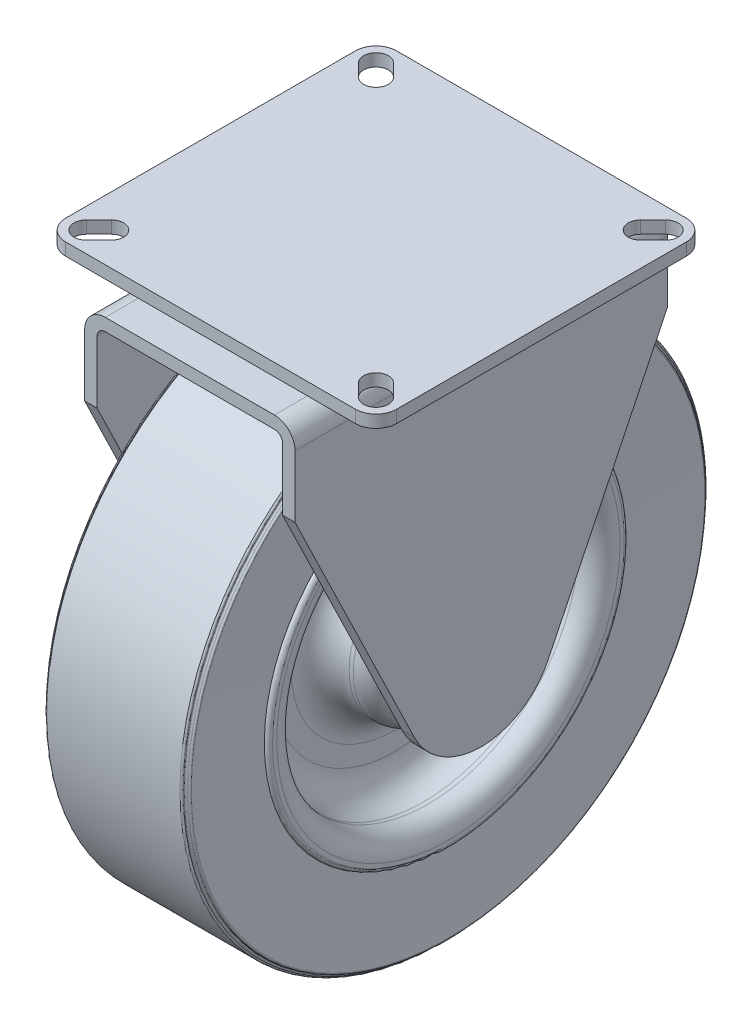
SolidWorks part; units mm, degrees
ref_plane "Front Plane" through (0, 0, 0) normal (0, 0, 1) x (1, 0, 0)
ref_plane "Top Plane" through (0, 0, 0) normal (0, 1, 0) x (1, 0, 0)
ref_plane "Right Plane" through (0, 0, 0) normal (1, 0, 0) x (0, 0, -1)
sketch "Sketch1" plane through (0, 0, 0) normal (0, 0, 1) x (1, 0, 0)
  line L0 (-16.5, 10) -> (16.5, 10)
  line L1 (-16.5, 43.5) -> (16.5, 43.5)
  line L2 (-17.5, 42.5) -> (-17.5, 11)
  line L3 (-25.7789, 0) -> (30.9257, 0) construction
  line L4 (17.5, 42.5) -> (17.5, 11)
  line L5 (11.5, 36.5) -> (12.5, 36.5)
  line L6 (-17.5, 10) -> (17.5, 10)
  line L7 (-17.5, 10) -> (-17.5, 13)
  line L8 (-12.5, 18) -> (-11.5, 18)
  line L9 (17.5, 10) -> (17.5, 13)
  line L10 (-17.5, 43.5) -> (17.5, 43.5)
  line L11 (-17.5, 43.5) -> (-17.5, 41.5)
  line L12 (-12.5, 36.5) -> (-11.5, 36.5)
  line L13 (17.5, 43.5) -> (17.5, 41.5)
  line L14 (11.5, 18) -> (12.5, 18)
  line L15 (-4.5, 29.5) -> (-4.5, 25)
  line L17 (4.5, 29.5) -> (4.5, 25)
  arc A0 (-17.5, 41.5) -> (-12.5, 36.5) centre (-12.5, 41.5) ccw
  arc A1 (17.5, 41.5) -> (12.5, 36.5) centre (12.5, 41.5) cw
  arc A2 (17.5, 13) -> (12.5, 18) centre (12.5, 13) ccw
  arc A3 (-17.5, 13) -> (-12.5, 18) centre (-12.5, 13) cw
  arc A4 (-16.5, 10) -> (-17.5, 11) centre (-16.5, 11) cw
  arc A5 (16.5, 10) -> (17.5, 11) centre (16.5, 11) ccw
  arc A6 (16.5, 43.5) -> (17.5, 42.5) centre (16.5, 42.5) cw
  arc A7 (-16.5, 43.5) -> (-17.5, 42.5) centre (-16.5, 42.5) ccw
  arc A8 (11.5, 18) -> (4.5, 25) centre (11.5, 25) cw
  arc A9 (-4.5, 25) -> (-11.5, 18) centre (-11.5, 25) cw
  arc A10 (-11.5, 36.5) -> (-4.5, 29.5) centre (-11.5, 29.5) cw
  arc A11 (11.5, 36.5) -> (4.5, 29.5) centre (11.5, 29.5) ccw
  point P0 (0, 0)
  point P21 (17.5, 36.5)
  point P24 (17.5, 18)
  point P41 (4.5, 18)
  dimension "D7" = 5
  dimension "D8" = 1
  dimension "D9" = 7
  dimension "D1" = 8
  dimension "D2" = 35
  dimension "D3" = 33.5
  dimension "D4" = 7
  dimension "D5" = 13
  dimension "D6" = 13
revolve "Revolve1" add sketch "Sketch1" angle 360 about L3 region at (0, 26.4263, 0)
sketch "Sketch2" plane through (0, 0, 0) normal (0, 0, 1) x (1, 0, 0)
  line L0 (-24.9917, 0) -> (28.5899, 0) construction
  line L2 (-16.5, 43.5) -> (16.5, 43.5)
  line L3 (-16.5, 62.9) -> (-16.5, 63.1)
  line L4 (-16.1, 63.5) -> (16.1, 63.5)
  line L5 (16.5, 62.9) -> (16.5, 63.1)
  line L7 (-16.5, 43.5) -> (-17.429, 62.08)
  line L10 (-16.5, 63.5) -> (-16.5, 62.5)
  line L11 (-16.9, 62.5) -> (-17.0295, 62.5)
  line L14 (16.9, 62.5) -> (17.0295, 62.5)
  line L15 (16.5, 43.5) -> (17.429, 62.08)
  arc A0 (-16.5, 63.1) -> (-16.1, 63.5) centre (-16.1, 63.1) cw
  arc A1 (-16.5, 62.9) -> (-16.9, 62.5) centre (-16.9, 62.9) cw
  arc A2 (-17.429, 62.08) -> (-17.0295, 62.5) centre (-17.0295, 62.1) cw
  arc A3 (17.429, 62.08) -> (17.0295, 62.5) centre (17.0295, 62.1) ccw
  arc A4 (16.9, 62.5) -> (16.5, 62.9) centre (16.9, 62.9) cw
  arc A5 (16.1, 63.5) -> (16.5, 63.1) centre (16.1, 63.1) cw
  point P23 (16.5, 62.5)
  point P30 (16.5, 63.5)
  dimension "D2" = 0.4
  dimension "D1" = 20
revolve "Revolve3" add sketch "Sketch2" angle 360 about L0 region at (0, 53.5699, 0)
sketch "Sketch5" plane through (0, 0, 0) normal (0, 0, 1) x (1, 0, 0)
  line L0 (-17.429, 62.08) -> (-17.429, -62.08) construction
  line L1 (22.429, -18) -> (25.429, -18)
  line L2 (-22.429, -15) -> (-22.429, 66.5)
  line L3 (-20.429, 68.5) -> (20.429, 68.5)
  line L4 (22.429, -15) -> (22.429, 66.5)
  line L5 (17.429, 62.08) -> (17.429, -62.08) construction
  line L6 (16.1, 63.5) -> (-16.1, 63.5) construction
  line L7 (-20.429, 71.5) -> (20.429, 71.5)
  line L8 (25.429, -18) -> (25.429, 66.5)
  line L9 (-25.429, -18) -> (-22.429, -18)
  line L10 (-25.429, -18) -> (-25.429, 66.5)
  line L11 (22.429, -15) -> (22.429, -18)
  line L12 (-22.429, -15) -> (-22.429, -18)
  line L13 (-22.429, -15) -> (22.429, -15) construction
  line L15 (-25.429, -18) -> (25.429, -18) construction
  arc A0 (-22.429, 66.5) -> (-20.429, 68.5) centre (-20.429, 66.5) cw
  arc A1 (20.429, 68.5) -> (22.429, 66.5) centre (20.429, 66.5) cw
  arc A2 (20.429, 71.5) -> (25.429, 66.5) centre (20.429, 66.5) cw
  arc A3 (-25.429, 66.5) -> (-20.429, 71.5) centre (-20.429, 66.5) cw
  dimension "D5" = 2
  dimension "D1" = 5
  dimension "D2" = 5
  dimension "D3" = 5
  dimension "D6" = 3
extrude "Boss-Extrude2" add sketch "Sketch5" along normal blind 90 from offset 45 separate body offset against normal yes
sketch "Sketch6" plane through (-25.429, 0, 0) normal (-1, 0, 0) x (0, 0, 1)
  line L0 (45, 66.5) -> (45, -18) construction
  line L5 (-45, 51.5) -> (-16.1938, -7.8587)
  line L6 (45, 51.5) -> (16.1938, -7.8587)
  line L7 (-45, 51.5) -> (-45, -18)
  line L8 (-45, -18) -> (45, -18)
  line L9 (45, -18) -> (45, 51.5)
  arc A0 (-16.1938, -7.8587) -> (16.1938, -7.8587) centre (0, 0) ccw
  line M1 (-45, 66.5) -> (-45, -18)
  line M2 (-45, -18) -> (45, -18)
  line M3 (45, -18) -> (45, 66.5)
extrude "Cut-Extrude1" cut sketch "Sketch6" against normal blind 3 contours A0 L8 L6 M3 | A0 L5 M1 M2 region at (-25.429, 4.7857, 33.3258) region at (-25.429, 4.7857, -33.3258)
extrude "Cut-Extrude2" cut sketch "Sketch6<3>" against normal through all from offset 47 contours A0 L8 L6 M3 | A0 L5 M1 M2 region at (-25.429, 4.7857, 33.3258) region at (-25.429, 4.7857, -33.3258) offset against normal yes
sketch "Sketch6<3>" plane through (-25.429, 0, 0) normal (-1, 0, 0) x (0, 0, 1) same geometry as "Sketch6"
sketch "Sketch7" plane through (-25.429, 0, 0) normal (-1, 0, 0) x (0, 0, 1)
  circle A0 centre (0, 0) radius 10
extrude "Boss-Extrude3" add sketch "Sketch7" against normal through all
sketch "Sketch8" plane through (0, 71.5, 0) normal (0, 1, 0) x (1, 0, 0)
  circle A0 centre (0, 0) radius 18
  circle A1 centre (0, 0) radius 20
extrude "Boss-Extrude4" add sketch "Sketch8" along normal blind 3
sketch "Sketch9" plane through (0, 74.5, 0) normal (0, 1, 0) x (1, 0, 0)
  line L1 (-35, 40) -> (35, 40)
  line L2 (-40, 35) -> (-40, -35)
  line L3 (-35, -40) -> (35, -40)
  line L4 (40, 35) -> (40, -35)
  line L5 (-40, 40) -> (40, -40) construction
  line L6 (-40, -40) -> (40, 40) construction
  arc A0 (35, -40) -> (40, -35) centre (35, -35) ccw
  arc A1 (-40, -35) -> (-35, -40) centre (-35, -35) ccw
  arc A2 (-35, 40) -> (-40, 35) centre (-35, 35) ccw
  arc A3 (35, 40) -> (40, 35) centre (35, 35) cw
  point P0 (0, 0)
  dimension "D3" = 5
  dimension "D1" = 80
  dimension "D2" = 80
extrude "Boss-Extrude5" add sketch "Sketch9" along normal blind 3
sketch "Sketch10" plane through (0, 77.5, 0) normal (0, 1, 0) x (1, 0, 0)
  line L0 (0, 45) -> (0, -45) construction
  line L1 (20.429, 45) -> (-20.429, 45) construction
  line L2 (20.429, -45) -> (-20.429, -45) construction
  line L3 (-40, 0) -> (40, 0) construction
  line L4 (-40, 35) -> (-40, -35) construction
  line L5 (40, -35) -> (40, 35) construction
  line L6 (35, 40) -> (-35, 40) construction
  line L7 (-37.1213, 32.8787) -> (-34.1213, 29.8787)
  line L8 (29.8787, 34.1213) -> (32.8787, 37.1213)
  line L9 (-29.8787, 34.1213) -> (-32.8787, 37.1213)
  line L10 (37.1213, 32.8787) -> (34.1213, 29.8787)
  line L11 (37.1213, -32.8787) -> (34.1213, -29.8787)
  line L12 (-29.8787, -34.1213) -> (-32.8787, -37.1213)
  line L13 (29.8787, -34.1213) -> (32.8787, -37.1213)
  line L14 (-37.1213, -32.8787) -> (-34.1213, -29.8787)
  arc A0 (-32.8787, 37.1213) -> (-37.1213, 32.8787) centre (-35, 35) ccw
  arc A1 (-34.1213, 29.8787) -> (-29.8787, 34.1213) centre (-32, 32) ccw
  arc A2 (34.1213, 29.8787) -> (29.8787, 34.1213) centre (32, 32) cw
  arc A3 (32.8787, 37.1213) -> (37.1213, 32.8787) centre (35, 35) cw
  arc A4 (32.8787, -37.1213) -> (37.1213, -32.8787) centre (35, -35) ccw
  arc A5 (34.1213, -29.8787) -> (29.8787, -34.1213) centre (32, -32) ccw
  arc A6 (-34.1213, -29.8787) -> (-29.8787, -34.1213) centre (-32, -32) cw
  arc A7 (-32.8787, -37.1213) -> (-37.1213, -32.8787) centre (-35, -35) cw
  dimension "D1" = 5
  dimension "D2" = 5
  dimension "D3" = 8
  dimension "D4" = 8
extrude "Cut-Extrude3" cut sketch "Sketch10" against normal blind 3
